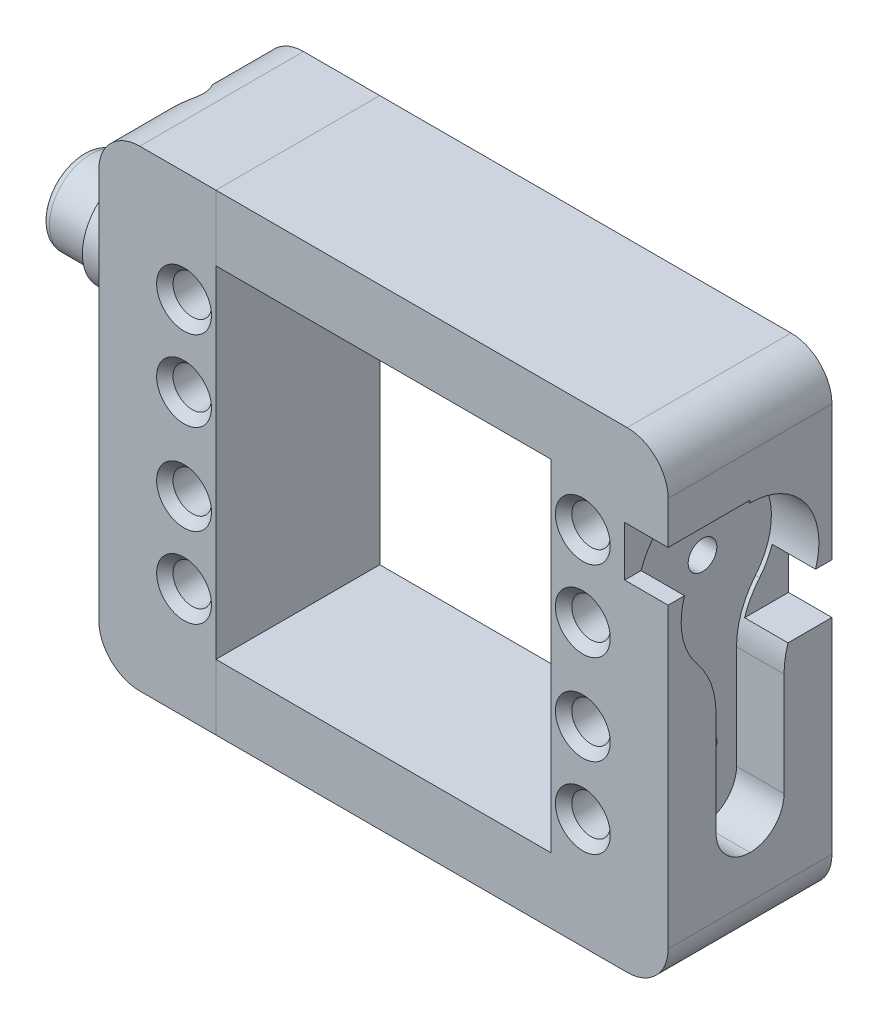
SolidWorks part; units mm, degrees
material "ABS"
ref_plane "Front Plane" through (0, 0, 0) normal (0, 0, 1) x (1, 0, 0)
ref_plane "Top Plane" through (0, 0, 0) normal (0, 1, 0) x (1, 0, 0)
ref_plane "Right Plane" through (0, 0, 0) normal (1, 0, 0) x (0, 0, -1)
sketch "Sketch1" plane through (0, 0, 0) normal (1, 0, 0) x (0, 0, -1)
  line L1 (-10, 10) -> (10, 10)
  line L2 (-10, 10) -> (-10, -10)
  line L3 (-10, -10) -> (10, -10)
  line L4 (10, 10) -> (10, -10)
  line L5 (-10, 10) -> (10, -10) construction
  line L6 (-10, -10) -> (10, 10) construction
  point P0 (0, 0)
  dimension "D1" = 20
  dimension "D2" = 20
extrude "Boss-Extrude1" add sketch "Sketch1" along normal blind 20
sketch "Sketch2" plane through (20, 0, 0) normal (1, 0, 0) x (0, 0, -1)
  line L1 (-10, 35) -> (10, 35)
  line L2 (-10, 35) -> (-10, -35)
  line L3 (-10, -35) -> (10, -35)
  line L4 (10, 35) -> (10, -35)
  line L5 (-10, 35) -> (10, -35) construction
  line L6 (-10, -35) -> (10, 35) construction
  point P0 (0, 0)
  dimension "D1" = 20
  dimension "D2" = 70
extrude "Boss-Extrude2" add sketch "Sketch2" along normal blind 10.3
sketch "Sketch4" plane through (30.3, 0, 0) normal (1, 0, 0) x (0, 0, -1)
  line L0 (0, 7.65) -> (0, 8.1702) construction
  line L1 (7.65, 7.65) -> (-7.65, 7.65) construction
  line L17 (4.15, -26.55) -> (-4.15, -26.55) construction
  line L18 (-7.65, 7.65) -> (7.65, 7.65) construction
  line L22 (-7.65, 7.65) -> (-7.65, -27.55) construction
  line L23 (-7.65, -27.55) -> (7.65, -27.55) construction
  line L24 (7.65, 7.65) -> (7.65, -27.55) construction
  line L25 (-7.65, 7.65) -> (7.65, -27.55) construction
  line L26 (-7.65, -27.55) -> (7.65, 7.65) construction
  line L27 (4.15, -26.55) -> (4.15, -28.55) construction
  line L28 (4.15, -28.55) -> (-4.15, -28.55) construction
  line L29 (-4.15, -26.55) -> (-4.15, -28.55) construction
  line L30 (4.15, -26.55) -> (-4.15, -28.55) construction
  line L31 (4.15, -28.55) -> (-4.15, -26.55) construction
  line L34 (4.15, -28.55) -> (-4.15, -28.55)
  line L35 (-4.15, -28.55) -> (-4.15, -7.3118)
  line L36 (4.15, -28.55) -> (4.15, -7.3118)
  arc A1 (4.15, -6.4265) -> (-4.15, -6.4265) centre (0, 0) ccw construction
  arc A2 (4.15, -7.3118) -> (-4.15, -7.3118) centre (0, 0) ccw
  point P1 (0, -27.55)
  point P7 (0, -13.75)
  point P10 (0, 7.65)
  point P14 (0, -9.95)
  dimension "D1" = 15.3
  dimension "D5" = 2
  dimension "D2" = 15.3
  dimension "D3" = 35.2
  dimension "D4" = 8.3
extrude "Cut-Extrude1" cut sketch "Sketch4" against normal blind 5.8
fillet "Fillet1" radius 4.15 2 edges at (27.4, -28.55, 4.15) (27.4, -28.55, -4.15)
fillet "Fillet2" radius 10 2 edges at (27.4, -7.3118, 4.15) (27.4, -7.3118, -4.15)
sketch "Sketch5" plane through (0, 0, 0) normal (-1, 0, 0) x (0, 0, 1)
  circle A0 centre (0, 0) radius 1.75
  dimension "D1" = 3.5
extrude "Cut-Extrude2" cut sketch "Sketch5" against normal through all
sketch "Sketch6" plane through (24.5, 0, 0) normal (1, 0, 0) x (0, 0, -1)
  line L0 (0, -19.35) -> (0, 0) construction
  line L1 (0, -25.65) -> (0, -23.15) construction
  line L2 (0, -23.15) -> (0, -21.85) construction
  line L3 (0, -21.85) -> (0, -19.35) construction
  line L5 (0, 0) -> (1.164, 0) construction
  line L6 (0, 0) -> (0, -9.35) construction
  line L7 (0, -9.35) -> (1.164, -9.35) construction
  line L8 (1.164, 0) -> (1.164, -9.35) construction
  line L9 (0, 0) -> (1.164, -9.35) construction
  line L10 (0, -9.35) -> (1.164, 0) construction
  circle A0 centre (0, -20.6) radius 1.75
  circle A1 centre (0, -9.35) radius 1.75 construction
  point P11 (0.582, -4.675)
  dimension "D5" = 3.5
  dimension "D6" = 9.35
  dimension "D7" = 3.5
  dimension "D1" = 19.35
  dimension "D2" = 2.5
  dimension "D3" = 1.3
  dimension "D4" = 2.5
extrude "Cut-Extrude3" cut sketch "Sketch6" against normal up to next
sketch "Sketch13" plane through (0, 0, 0) normal (-1, 0, 0) x (0, 0, 1)
  line L1 (-10, 10) -> (10, 10)
  line L2 (-10, 10) -> (-10, -10)
  line L3 (-10, -10) -> (10, -10)
  line L4 (10, 10) -> (10, -10)
extrude "Cut-Extrude9" cut sketch "Sketch13" against normal up to surface (20 mm away) up to face at (20, 22.5, 0)
sketch "Sketch29" plane through (30.3, 0, 0) normal (1, 0, 0) x (0, 0, -1)
  line L0 (0, 0) -> (0, 2.6) construction
  line L1 (15.1094, -8.7) -> (15.1094, -2.6)
  line L2 (0, 2.6) -> (-15.1094, 2.6)
  line L4 (0, 2.6) -> (0, 3.8)
  line L5 (0, 3.8) -> (0, 7.5)
  line L6 (0, 7.5) -> (0, 8.7)
  line L7 (0, 8.7) -> (-15.1094, 8.7)
  line L8 (-15.1094, 8.7) -> (-15.1094, 2.6)
  line L9 (0, -2.6) -> (15.1094, -2.6)
  line L10 (0, -2.6) -> (0, -3.8)
  line L11 (0, -3.8) -> (0, -7.5)
  line L12 (0, -7.5) -> (0, -8.7)
  line L13 (0, -8.7) -> (15.1094, -8.7)
  point P19 (0, 0)
  dimension "D1" = 2.6
  dimension "D2" = 1.2
  dimension "D3" = 3.7
  dimension "D4" = 1.2
  dimension "D5" = 2
extrude "Cut-Extrude18" cut sketch "Sketch29" against normal blind 5.3
sketch "Sketch32" plane through (30.3, 0, 0) normal (1, 0, 0) x (0, 0, -1)
  line L0 (0, -28.55) -> (0, -38.725) construction
  line L1 (10, -35) -> (10, -8.7) construction
  line L2 (-10, -35) -> (10, -35)
  line L3 (-10, -35) -> (-10, -38.725)
  line L4 (-10, -38.725) -> (10, -38.725)
  line L5 (10, -35) -> (10, -38.725)
  dimension "D1" = 10.175
extrude "Boss-Extrude3" add sketch "Sketch32" against normal up to surface (10.3 mm away) up to face at (20, 0, 0)
sketch "Sketch31" plane through (30.3, 0, 0) normal (1, 0, 0) x (0, 0, -1)
  line L2 (0, 8.7) -> (0, 18.875) construction
  line L3 (10, -2.6) -> (10, 35) construction
  line L4 (-10, 35) -> (10, 35)
  line L5 (-10, 35) -> (-10, 18.875)
  line L6 (-10, 18.875) -> (10, 18.875)
  line L7 (10, 35) -> (10, 18.875)
  dimension "D1" = 10.175
extrude "Cut-Extrude19" cut sketch "Sketch31" against normal through all
sketch "Sketch34" plane through (20, 0, 0) normal (-1, 0, 0) x (0, 0, 1)
  line L4 (10, -38.725) -> (10, 18.875)
  line L5 (10, 18.875) -> (-10, 18.875)
  line L6 (-10, 18.875) -> (-10, -38.725)
  line L7 (-10, -38.725) -> (10, -38.725)
  line L8 (10, -38.725) -> (10, 18.875)
  line L9 (10, 18.875) -> (-10, 18.875)
  line L10 (-10, 18.875) -> (-10, -38.725)
  line L11 (-10, -38.725) -> (10, -38.725)
  circle A0 centre (0, -20.6) radius 1.75 construction
  circle A1 centre (0, 0) radius 1.75 construction
  circle A2 centre (0, -20.6) radius 1.75
  circle A3 centre (0, 0) radius 1.75
  dimension "D1" = 0
extrude "Boss-Extrude5" add sketch "Sketch34" along normal blind 4
sketch "Sketch35" plane through (16, 0, 0) normal (-1, 0, 0) x (0, 0, 1)
  line L0 (10, -38.725) -> (10, 18.875) construction
  line L1 (-10, 18.875) -> (10, 18.875)
  line L2 (-10, 18.875) -> (-10, 10.875)
  line L3 (-10, 10.875) -> (10, 10.875)
  line L4 (10, 18.875) -> (10, 10.875)
  line L5 (0, 10.875) -> (0, -30.725) construction
  line L6 (-10, -38.725) -> (10, -38.725)
  line L7 (-10, -38.725) -> (-10, -30.725)
  line L8 (-10, -30.725) -> (10, -30.725)
  line L9 (10, -38.725) -> (10, -30.725)
  dimension "D1" = 41.6
extrude "Boss-Extrude6" add sketch "Sketch35" along normal blind 40.9
sketch "Sketch37" plane through (-24.9, 0, 0) normal (-1, 0, 0) x (0, 0, 1)
  line L1 (-10, 18.875) -> (10, 18.875)
  line L2 (-10, 18.875) -> (-10, -38.725)
  line L3 (-10, -38.725) -> (10, -38.725)
  line L4 (10, 18.875) -> (10, -38.725)
extrude "Boss-Extrude7" add sketch "Sketch37" along normal blind 14.3
sketch "Sketch38" plane through (0, 0, 10) normal (0, 0, 1) x (1, 0, 0)
  line L0 (-24.9, 10.875) -> (-24.9, -9.925) construction
  line L1 (-24.9, -9.925) -> (-24.9, -30.725) construction
  line L2 (-24.9, -30.725) -> (-24.9, 10.875) construction
  line L3 (-24.9, -9.925) -> (-39.2, -9.925) construction
  line L4 (-39.2, -38.725) -> (-39.2, 18.875) construction
  line L5 (-24.9, 0.475) -> (-28.79, 0.475) construction
  line L6 (-28.79, 0.475) -> (-28.79, 5.375) construction
  line L7 (-24.9, 10.875) -> (16, 10.875) construction
  line L8 (-4.45, 10.875) -> (-4.45, -38.725) construction
  line L9 (-39.2, -38.725) -> (30.3, -38.725) construction
  circle A0 centre (-28.79, 5.375) radius 2.35
  circle A1 centre (-28.79, -4.425) radius 2.35
  circle A2 centre (-28.79, -25.225) radius 2.35
  circle A3 centre (-28.79, -15.425) radius 2.35
  circle A4 centre (19.89, 5.375) radius 2.35
  circle A5 centre (19.89, -4.425) radius 2.35
  circle A6 centre (19.89, -15.425) radius 2.35
  circle A7 centre (19.89, -25.225) radius 2.35
  dimension "D4" = 4.7
  dimension "D1" = 41.6
  dimension "D2" = 3.89
  dimension "D3" = 4.9
extrude "Cut-Extrude20" cut sketch "Sketch38" against normal blind 8
chamfer "Chamfer1" distance 1 angle 45 8 edges at (22.24, -25.225, 10) (17.54, -15.425, 10) (22.24, -4.425, 10) (17.54, 5.375, 10) (-26.44, 5.375, 10) (-26.44, -15.425, 10) (-31.14, -25.225, 10) (-31.14, -4.425, 10)
sketch "Sketch41" plane through (16, 0, 0) normal (-1, 0, 0) x (0, 0, 1)
  circle A0 centre (0, 0) radius 3.5
  circle A1 centre (0, -20.6) radius 3.5
  dimension "D1" = 7
  dimension "D2" = 7
extrude "Cut-Extrude23" cut sketch "Sketch41" against normal blind 4
sketch "Sketch42" plane through (-39.2, 0, 0) normal (-1, 0, 0) x (0, 0, 1)
  line L0 (10, -38.725) -> (10, 18.875) construction
  line L1 (-10, -38.725) -> (10, -38.725) construction
  line L2 (-10, -38.725) -> (-10, -30.725) construction
  line L3 (-10, -30.725) -> (10, -30.725) construction
  line L4 (10, -38.725) -> (10, -30.725) construction
  line L5 (-10, -9.925) -> (10, -9.925) construction
  line L6 (-10, 18.875) -> (-10, -38.725) construction
  circle A0 centre (0, -34.725) radius 1.75
  circle A1 centre (0, 14.875) radius 1.75
  point P9 (-10, -34.725)
  dimension "D2" = 3.5
  dimension "D1" = 8
  dimension "D3" = 4
  dimension "D4" = 10
extrude "Cut-Extrude24" cut sketch "Sketch42" against normal blind 22.3
sketch "Sketch43" plane through (-39.2, 0, 0) normal (-1, 0, 0) x (0, 0, 1)
  circle A0 centre (0, 14.875) radius 3.5
  circle A1 centre (0, -34.725) radius 3.5
  dimension "D1" = 7
  dimension "D2" = 7
extrude "Cut-Extrude25" cut sketch "Sketch43" against normal blind 11
fillet "Fillet3" radius 5 4 edges at (-39.2, -38.725, 0) (30.3, -38.725, 0) (30.3, 18.875, 0) (-39.2, 18.875, 0)
sketch "Sketch44" plane through (0, 0, 10) normal (0, 0, 1) x (1, 0, 0)
  line L0 (-24.9, 18.875) -> (-24.9, -38.725)
  line L1 (-34.2, 18.875) -> (25.3, 18.875) construction
  line L2 (-34.2, -38.725) -> (25.3, -38.725) construction
split "Split1" trim tools "Sketch44" bodies to split 171 resulting bodies 172 173
sketch "Sketch45" plane through (-24.9, 0, 0) normal (-1, 0, 0) x (0, 0, 1)
  circle A0 centre (0, 14.875) radius 2.35
  circle A1 centre (0, -34.725) radius 2.35
  dimension "D1" = 4.7
  dimension "D2" = 4.7
extrude "Cut-Extrude26" cut sketch "Sketch45" against normal blind 8
chamfer "Chamfer2" distance 1 angle 45 2 edges at (-24.9, -34.725, 2.35) (-24.9, 14.875, 2.35)
sketch "Sketch46" plane through (-39.2, 0, 0) normal (-1, 0, 0) x (0, 0, 1)
  circle A1 centre (0, 0) radius 5.025
  dimension "D1" = 10.05
extrude "Boss-Extrude8" add sketch "Sketch46" along normal blind 12
fillet "Fillet5" radius 1 1 edges at (-51.2, 0, 5.025)
sketch "Sketch50" plane through (-39.2, 0, 0) normal (-1, 0, 0) x (0, 0, 1)
  circle A0 centre (0, 0) radius 6
  dimension "D1" = 12
extrude "Boss-Extrude9" add sketch "Sketch50" along normal blind 6
fillet "Fillet6" radius 3 1 edges at (-39.2, 0, 6)
mirror "Mirror1" [suppressed] of bodies 177 174 167 172 173
delete or keep bodies "Body-Delete/Keep 1" [suppressed] type delete bodies bodies 177 174
sketch "Sketch47" plane through (0, 0, 10) normal (0, 0, 1) x (1, 0, 0)
  line L0 (19.89, 5.375) -> (19.89, -4.425)
  line L1 (19.89, 0.475) -> (28.8988, 0.475)
sketch "Sketch48" plane through (24.5, 0, 0) normal (1, 0, 0) x (0, 0, -1)
  line L0 (0, 0) -> (-13.129, 0)
  line L1 (-10, 8.725) -> (-10, 2.025) construction
sketch "Sketch49" plane through (0, 0, 10) normal (0, 0, 1) x (1, 0, 0)
  line L0 (24.5491, 0) -> (24.5491, 0.475)
  line L1 (19.89, 0.475) -> (28.8988, 0.475) construction
